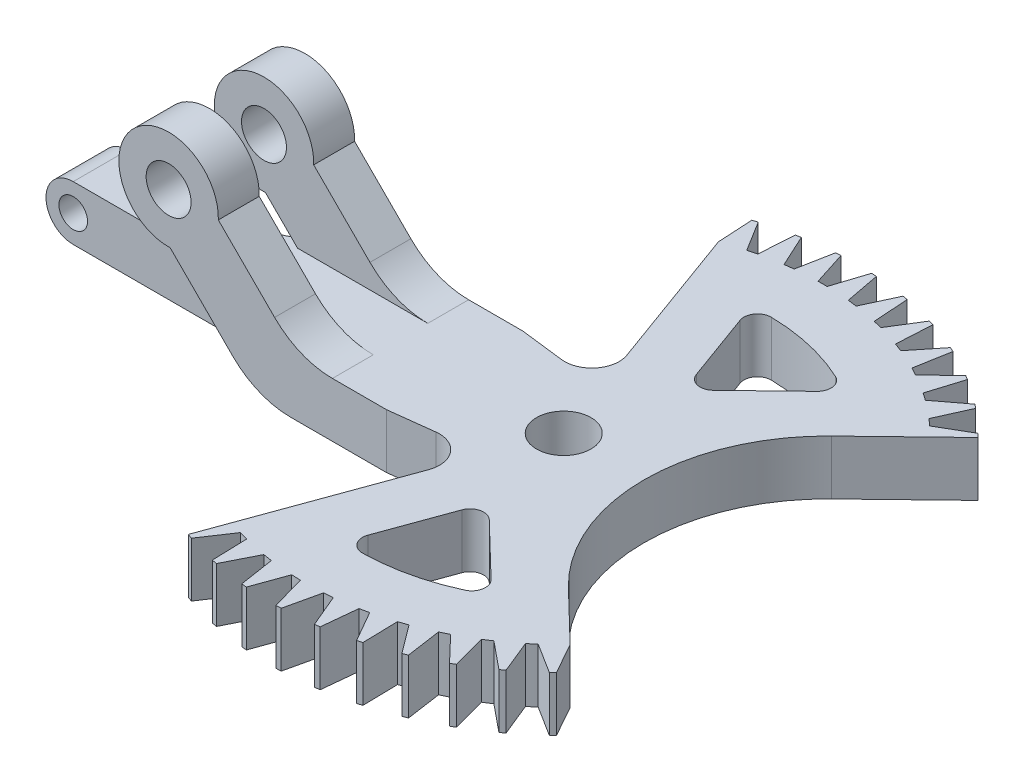
SolidWorks part; units mm, degrees
ref_plane "Front Plane" through (0, 0, 0) normal (0, 0, 1) x (1, 0, 0)
ref_plane "Top Plane" through (0, 0, 0) normal (0, 1, 0) x (1, 0, 0)
ref_plane "Right Plane" through (0, 0, 0) normal (1, 0, 0) x (0, 0, -1)
sketch "Sketch1" plane through (0, 0, 0) normal (0, 0, 1) x (1, 0, 0)
  line L0 (6.4645, -10) -> (16, -10)
  line L1 (16, -10) -> (16, -6)
  line L2 (16, -6) -> (9.5355, -6)
  line L3 (9.5355, -6) -> (3.6483, -0.1127)
  line L4 (6.4645, -10) -> (0.1127, -3.6483)
  line L5 (0, 0) -> (14.0151, -14.0151) construction
  line L6 (0, 0) -> (0, -20.1214) construction
  circle A0 centre (0, 0) radius 1.65
  arc A1 (3.6483, -0.1127) -> (0.1127, -3.6483) centre (0, 0) ccw
  arc A2 (2.5809, -2.5809) -> (3.6483, -0.1127) centre (0, 0) ccw construction
  arc A3 (0.1127, -3.6483) -> (2.5809, -2.5809) centre (0, 0) ccw construction
  circle A4 centre (0, 0) radius 3.65 construction
  point P5 (4, 0)
  dimension "D1" = 3.3
  dimension "D3" = 4
  dimension "D4" = 5
  dimension "D5" = 16
  dimension "D6" = 6
  dimension "D7" = 45
  dimension "D2" = 2
extrude "Boss-Extrude1" add sketch "Sketch1" along normal mid plane 10
sketch "Sketch3" plane through (0, -10, 0) normal (0, -1, 0) x (1, 0, 0)
  line L0 (-3.65, -5) -> (3.65, -5) construction
  line L1 (3.65, 5) -> (-3.65, 5) construction
  line L4 (6.4645, -5) -> (6.4645, 5) construction
  line L6 (-3.65, -5) -> (3.65, -5) construction
  line L7 (3.65, 5) -> (-3.65, 5) construction
  line L8 (6.4645, 2) -> (-3.65, 2)
  line L9 (-3.65, 2) -> (-3.65, -2)
  line L10 (6.4645, -2) -> (6.4645, 2)
  line L11 (-3.65, -2) -> (6.4645, -2)
  line L12 (0, 0) -> (-8.9484, 0) construction
  line L13 (6.4645, 2) -> (6.4645, 5) construction
  line L14 (6.4645, -5) -> (6.4645, -2) construction
  dimension "D1" = 4
extrude "Cut-Extrude1" cut sketch "Sketch3" against normal through all
sketch "Sketch4" plane through (0, -10, 0) normal (0, -1, 0) x (1, 0, 0)
  line L0 (16, 5) -> (16, -5) construction
  line L1 (16, 5) -> (16, -5)
  line L2 (0, 0) -> (22, 0) construction
  line L4 (16, -5) -> (19.2309, -4.608)
  line L5 (24, -40.1964) -> (24, 20.3832) construction
  line L8 (20, 0) -> (22, 0) construction
  line L9 (24, 0) -> (15.4238, -23.5629) construction
  line L10 (21.3512, -7.2775) -> (16.6466, -20.2034)
  line L11 (34, -9.6569) -> (39.4658, -14.9352)
  line L12 (26, 0) -> (28, 0) construction
  line L13 (22, 0) -> (24, 0) construction
  line L14 (24, -4.0293) -> (24.4818, -3.9709) construction
  line L15 (22.4657, -4.2155) -> (24, -4.0293) construction
  line L16 (24, 0) -> (26, 0) construction
  line L17 (16, 5) -> (19.2309, 4.608)
  line L18 (21.3512, 7.2775) -> (16.6466, 20.2034)
  line L19 (34, 9.6569) -> (39.4658, 14.9352)
  line L20 (16, 0) -> (20, 0) construction
  line L21 (26, 0) -> (33.4439, 0) construction
  line L22 (24, 0) -> (26, 0) construction
  line L23 (22, 0) -> (24, 0) construction
  line L24 (34, 9.6569) -> (34, -9.6569) construction
  circle A0 centre (24, 0) radius 2
  arc A1 (27.873, 1) -> (28, 0) centre (24, 0) ccw construction
  arc A2 (20, 0) -> (24.4818, -3.9709) centre (24, 0) ccw construction
  arc A3 (21.1226, 2.7786) -> (20, 0) centre (24, 0) ccw construction
  circle A4 centre (24, 0) radius 4 construction
  arc A5 (16.6466, -20.2034) -> (39.4658, -14.9352) centre (24, 0) ccw
  arc A7 (34, 9.6569) -> (34, -9.6569) centre (43.3255, 0) ccw
  arc A8 (24.4818, -3.9709) -> (21.1226, 2.7786) centre (24, 0) ccw construction
  arc A12 (21.3512, -7.2775) -> (19.2309, -4.608) centre (19.4718, -6.5934) ccw
  arc A13 (27.873, 1) -> (27.873, -1) centre (24, 0) ccw construction
  arc A14 (24, 2) -> (22, 0) centre (24, 0) ccw construction
  arc A15 (26, 0) -> (24, 2) centre (24, 0) ccw construction
  circle A16 centre (24, 0) radius 2 construction
  arc A17 (21.3512, 7.2775) -> (19.2309, 4.608) centre (19.4718, 6.5934) cw
  arc A19 (16.6466, 20.2034) -> (39.4658, 14.9352) centre (24, 0) cw
  arc A20 (34, -9.6569) -> (34, 9.6569) centre (43.3255, 0) ccw construction
  point P10 (28, 0)
  point P16 (25.9126, 0.5847)
  dimension "D1" = 4
  dimension "D4" = 43
  dimension "D5" = 1
  dimension "D6" = 2
  dimension "D2" = 8
  dimension "D7" = 20
  dimension "D8" = 46
  dimension "D9" = 10
  dimension "D3" = 2
extrude "Boss-Extrude2" add sketch "Sketch4" against normal up to surface (4 mm away) up to face at (12.7678, -6, 0)
sketch "Sketch5" plane through (0, 0, 0) normal (0, 0, 1) x (1, 0, 0)
  line L2 (6.4645, -10) -> (-10, -10)
  line L3 (9.5355, -6) -> (-10, -6)
  line L4 (16, -6) -> (9.5355, -6) construction
  line L5 (16, -6) -> (9.5355, -6)
  line L6 (6.4645, -10) -> (16, -10) construction
  line L7 (6.4645, -10) -> (16, -10)
  line L8 (16, -10) -> (16, -6)
  arc A2 (-10, -6) -> (-10, -10) centre (-10, -8) ccw
  circle A3 centre (-10, -8) radius 1.05
  arc A4 (-10, -10) -> (-10, -6) centre (-10, -8) ccw construction
  dimension "D2" = 2.1
  dimension "D1" = 10
extrude "Boss-Extrude3" add sketch "Sketch5" along normal mid plane 4
sketch "Sketch6" plane through (0, -10, 0) normal (0, -1, 0) x (1, 0, 0)
  line L0 (34, 9.6569) -> (39.4658, 14.9352) construction
  line L1 (16.6466, 20.2034) -> (21.3512, 7.2775) construction
  line L2 (34, 9.6569) -> (37.6675, 13.1985) construction
  line L3 (17.5016, 17.8542) -> (21.3512, 7.2775) construction
  line L4 (37.6675, 13.1985) -> (39.4658, 14.9352) construction
  line L5 (16.6466, 20.2034) -> (17.5016, 17.8542) construction
  line L6 (24, 0) -> (44.1554, 16.9124) construction
  line L7 (24, 0) -> (41.5141, 18.1364) construction
  line L8 (24, 0) -> (38.1198, 12.7135) construction
  line L9 (38.9352, 15.4658) -> (37.6675, 13.1985)
  line L10 (40.47, 13.8199) -> (38.1198, 12.7135)
  arc A0 (37.6675, 13.1985) -> (17.5016, 17.8542) centre (24, 0) ccw construction
  arc A1 (39.4658, 14.9352) -> (16.6466, 20.2034) centre (24, 0) ccw construction
  arc A2 (40.47, 13.8199) -> (38.9352, 15.4658) centre (24, 0) ccw
  arc A3 (38.1198, 12.7135) -> (37.6675, 13.1985) centre (24, 0) ccw
  arc A4 (38.9352, 15.4658) -> (16.6466, 20.2034) centre (24, 0) ccw construction
  arc A5 (17.5016, 17.8542) -> (38.5548, 12.213) centre (24, 0) ccw construction
  arc A6 (38.5548, 12.213) -> (38.1198, 12.7135) centre (24, 0) ccw construction
  dimension "D1" = 2.5
  dimension "D2" = 4
  dimension "D3" = 2
  dimension "D4" = 2
extrude "Cut-Extrude2" cut sketch "Sketch6" against normal up to next
sketch "Sketch8" plane through (0, -6, 0) normal (0, 1, 0) x (1, 0, 0)
  line L0 (6.4645, -2) -> (3.6483, -2) construction
  line L1 (6.4645, 2) -> (6.4645, -2) construction
  line L2 (3.6483, 2) -> (6.4645, 2) construction
  line L3 (9.5355, -5) -> (9.5355, 5) construction
  line L4 (9.5355, -2) -> (6.4645, -2)
  line L5 (6.4645, 2) -> (6.4645, -2)
  line L6 (6.4645, 2) -> (9.5355, 2)
  line L7 (9.5355, -2) -> (9.5355, 2)
  line L8 (3.6483, 2) -> (6.4645, 2) construction
  line L9 (9.5355, 2) -> (9.5355, 5) construction
  line L10 (9.5355, -5) -> (9.5355, -2) construction
  line L11 (6.4645, -2) -> (3.6483, -2) construction
extrude "Cut-Extrude4" cut sketch "Sketch8" along normal blind 4
pattern_circular "CirPattern1" count 10 every 7 about axis through (24, 0, 0) along (0, 1, 0) of "Cut-Extrude2"
sketch "Sketch7" plane through (0, -10, 0) normal (0, -1, 0) x (1, 0, 0)
  line L0 (21.3512, -7.2775) -> (16.6466, -20.2034) construction
  line L1 (21.3512, -7.2775) -> (17.5016, -17.8542) construction
  line L2 (24, 0) -> (12.9046, -24.9206) construction
  line L3 (24, 0) -> (14.8835, -28.0578) construction
  line L4 (24, 0) -> (16.8825, -17.6165) construction
  line L5 (17.5016, -17.8542) -> (16.6466, -20.2034) construction
  line L6 (15.2552, -19.6412) -> (16.8825, -17.6165)
  line L7 (17.3561, -20.4477) -> (17.5016, -17.8542)
  arc A0 (16.8825, -17.6165) -> (17.5016, -17.8542) centre (24, 0) ccw
  arc A1 (16.6466, -20.2034) -> (39.4658, -14.9352) centre (24, 0) ccw construction
  arc A2 (15.2552, -19.6412) -> (17.3561, -20.4477) centre (24, 0) ccw
  arc A3 (17.3561, -20.4477) -> (39.4658, -14.9352) centre (24, 0) ccw construction
  arc A4 (18.1287, -18.0701) -> (16.272, -17.3574) centre (24, 0) ccw construction
  arc A5 (16.272, -17.3574) -> (16.8825, -17.6165) centre (24, 0) ccw construction
  arc A6 (17.5016, -17.8542) -> (18.1287, -18.0701) centre (24, 0) ccw construction
  dimension "D1" = 2.5
  dimension "D2" = 4
  dimension "D3" = 2
  dimension "D4" = 2
extrude "Cut-Extrude3" cut sketch "Sketch7" against normal up to next
pattern_circular "CirPattern2" count 10 every 7 about axis through (24, 0, 0) along (0, 1, 0) of "Cut-Extrude3"
fillet "Fillet1" radius 6 4 edges at (6.4645, -10, -3.5) (6.4645, -10, 3.5) (9.5355, -6, 3.5) (9.5355, -6, -3.5)
fillet "Fillet2" radius 2 4 edges at (6.6536, -9.5433, -2) (6.6536, -9.5433, 2) (3.5858, -7.1213, -2) (3.5858, -7.1213, 2)
sketch "Sketch9" plane through (0, -6, 0) normal (0, 1, 0) x (1, 0, 0)
  line L0 (21.3512, -7.2775) -> (16.6466, -20.2034) construction
  line L1 (37.6675, -13.1985) -> (34, -9.6569) construction
  line L2 (21.3512, -7.2775) -> (16.6466, -20.2034) construction
  line L3 (37.6675, -13.1985) -> (34, -9.6569) construction
  line L4 (25.1254, -8.6031) -> (23.2863, -13.6562)
  line L5 (30.628, -11.9612) -> (26.7598, -8.2258)
  line L6 (25.11, -8.6455) -> (20.4053, -21.5715) construction
  line L7 (34.8888, -16.0759) -> (31.2214, -12.5342) construction
  line L9 (22.8142, -14.9531) -> (20.4053, -21.5715) construction
  line L10 (34.8888, -16.0759) -> (31.6207, -12.9199) construction
  arc A0 (27.6254, -18.6509) -> (28.2741, -18.513) centre (24, 0) ccw construction
  arc A1 (27.6254, -18.6509) -> (28.2741, -18.513) centre (24, 0) ccw construction
  arc A2 (24.2421, -14.998) -> (30.3571, -13.5863) centre (24, 0) ccw
  arc A3 (26.8621, -14.7244) -> (27.3743, -14.6156) centre (24, 0) ccw construction
  arc A4 (24.2421, -14.998) -> (23.2863, -13.6562) centre (24.226, -13.9982) cw
  arc A5 (30.3571, -13.5863) -> (30.628, -11.9612) centre (29.9333, -12.6805) ccw
  arc A6 (26.7598, -8.2258) -> (25.1254, -8.6031) centre (26.0651, -8.9451) ccw
  point P14 (26.2227, -5.5883)
  dimension "D2" = 1
  dimension "D1" = 4
extrude "Cut-Extrude5" cut sketch "Sketch9" against normal up to next
mirror "Mirror1" about plane through (0, 0, 0) normal (0, 0, 1) of "Cut-Extrude5"
